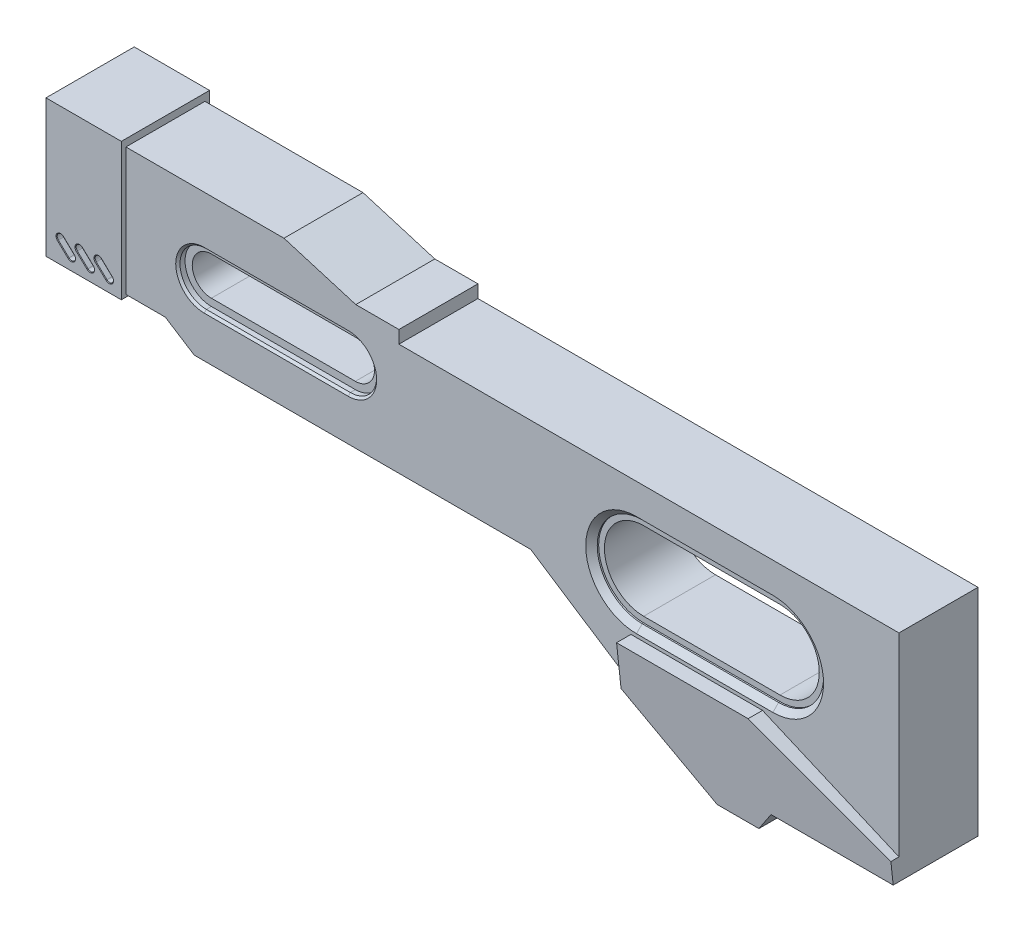
SolidWorks part; units mm, degrees
ref_plane "Front Plane" through (0, 0, 0) normal (0, 0, 1) x (1, 0, 0)
ref_plane "Top Plane" through (0, 0, 0) normal (0, 1, 0) x (1, 0, 0)
ref_plane "Right Plane" through (0, 0, 0) normal (1, 0, 0) x (0, 0, -1)
sketch "Sketch1" plane through (0, 0, 0) normal (0, 0, 1) x (1, 0, 0)
  line L0 (99.5486, 206.6349) -> (132.842, 206.6349)
  line L1 (132.842, 206.6349) -> (132.842, 207.688)
  line L2 (132.842, 207.688) -> (150.2564, 207.688)
  line L3 (150.2564, 207.688) -> (163.0366, 199.5431)
  line L4 (163.0366, 199.5431) -> (311.6766, 199.5431)
  line L5 (311.6766, 199.5431) -> (395.7493, 144.6965)
  line L6 (395.7493, 144.6965) -> (414.1914, 144.6965)
  line L7 (414.1914, 144.6965) -> (420.505, 153.713)
  line L8 (420.505, 153.713) -> (474.5094, 153.713)
  line L9 (474.5094, 153.713) -> (474.5094, 248.963)
  line L10 (474.5094, 248.963) -> (132.842, 248.963)
  line L11 (132.842, 248.963) -> (132.842, 251.0849)
  line L12 (132.842, 251.0849) -> (99.5486, 251.0849)
  line L13 (99.5486, 251.0849) -> (99.5486, 206.6349)
  dimension "D1" = 44.45
  dimension "D2" = 33.2933
  dimension "D3" = 33.2933
  dimension "D4" = 41.275
  dimension "D5" = 17.4144
  dimension "D6" = 15.155
  dimension "D7" = 49.4199
  dimension "D8" = 95.25
  dimension "D9" = 18.442
  dimension "D10" = 54.0045
  dimension "D11" = 100.3811
  dimension "D12" = 11.0073
  dimension "D13" = 148.64
  dimension "D14" = 1.0531
extrude "Boss-Extrude1" add sketch "Sketch1" along normal blind 17.4625 and the other way blind 17.4625 contours L10 L11 L12 L13 L0 L1 L2 L3 L4 L5 L6 L7 L8 L9
sketch "Sketch3" plane through (0, 0, 17.4625) normal (0, 0, 1) x (1, 0, 0)
  line L1 (99.5486, 251.0849) -> (132.842, 251.0849)
  line L2 (99.5486, 251.0849) -> (99.5486, 206.6349)
  line L3 (99.5486, 206.6349) -> (132.842, 206.6349)
  line L4 (132.842, 251.0849) -> (132.842, 206.6349)
extrude "Boss-Extrude2" add sketch "Sketch3" along normal blind 2.032
sketch "Sketch4" plane through (0, 0, -17.4625) normal (0, 0, -1) x (-1, 0, 0)
  line L1 (-99.5486, 251.0849) -> (-132.842, 251.0849)
  line L2 (-99.5486, 251.0849) -> (-99.5486, 206.6349)
  line L3 (-99.5486, 206.6349) -> (-132.842, 206.6349)
  line L4 (-132.842, 251.0849) -> (-132.842, 206.6349)
extrude "Boss-Extrude3" add sketch "Sketch4" along normal blind 2.032
sketch "Sketch8" plane through (0, 0, 17.4625) normal (0, 0, 1) x (1, 0, 0)
  line L0 (358.4861, 213.0728) -> (418.7637, 213.0728) construction
  line L1 (358.4861, 230.4099) -> (418.7637, 230.4099)
  line L2 (358.4861, 195.7357) -> (418.7637, 195.7357)
  line L3 (231.074, 230.4099) -> (167.4295, 230.4099) construction
  line L4 (231.074, 221.9555) -> (167.4295, 221.9555)
  line L5 (231.074, 238.8642) -> (167.4295, 238.8642)
  arc A0 (358.4861, 230.4099) -> (358.4861, 195.7357) centre (358.4861, 213.0728) ccw
  arc A1 (418.7637, 195.7357) -> (418.7637, 230.4099) centre (418.7637, 213.0728) ccw
  arc A2 (231.074, 221.9555) -> (231.074, 238.8642) centre (231.074, 230.4099) ccw
  arc A3 (167.4295, 238.8642) -> (167.4295, 221.9555) centre (167.4295, 230.4099) ccw
  point P2 (388.6249, 213.0728)
  point P9 (199.2518, 230.4099)
extrude "Cut-Extrude4" cut sketch "Sketch8" against normal through all
sketch "Sketch9" plane through (0, 0, 19.4945) normal (0, 0, 1) x (1, 0, 0)
  line L0 (105.9514, 216.6136) -> (110.6596, 212.1469) construction
  line L1 (107.1264, 217.8522) -> (111.8347, 213.3854)
  line L2 (104.7763, 215.3751) -> (109.4845, 210.9083)
  line L3 (114.3334, 216.6136) -> (119.0416, 212.1469) construction
  line L4 (115.5084, 217.8522) -> (120.2167, 213.3854)
  line L5 (113.1583, 215.3751) -> (117.8665, 210.9083)
  line L6 (122.7154, 216.6136) -> (127.4236, 212.1469) construction
  line L7 (123.8904, 217.8522) -> (128.5987, 213.3854)
  line L8 (121.5403, 215.3751) -> (126.2485, 210.9083)
  arc A0 (107.1264, 217.8522) -> (104.7763, 215.3751) centre (105.9514, 216.6136) ccw
  arc A1 (109.4845, 210.9083) -> (111.8347, 213.3854) centre (110.6596, 212.1469) ccw
  arc A2 (115.5084, 217.8522) -> (113.1583, 215.3751) centre (114.3334, 216.6136) ccw
  arc A3 (117.8665, 210.9083) -> (120.2167, 213.3854) centre (119.0416, 212.1469) ccw
  arc A4 (123.8904, 217.8522) -> (121.5403, 215.3751) centre (122.7154, 216.6136) ccw
  arc A5 (126.2485, 210.9083) -> (128.5987, 213.3854) centre (127.4236, 212.1469) ccw
  point P2 (108.3055, 214.3802)
  point P10 (116.6875, 214.3802)
  point P17 (125.0695, 214.3802)
  dimension "D1" = 3
extrude "Cut-Extrude5" cut sketch "Sketch9" against normal blind 2.54
sketch "Sketch10" plane through (0, 0, 17.4625) normal (0, 0, 1) x (1, 0, 0)
  line L8 (167.4295, 218.7805) -> (231.074, 218.7805)
  line L9 (231.074, 242.0392) -> (167.4295, 242.0392)
  line L10 (167.4295, 218.7805) -> (231.074, 218.7805)
  line L11 (231.074, 242.0392) -> (167.4295, 242.0392)
  arc A6 (231.074, 218.7805) -> (231.074, 242.0392) centre (231.074, 230.4099) ccw
  arc A7 (167.4295, 242.0392) -> (167.4295, 218.7805) centre (167.4295, 230.4099) ccw
  arc A8 (231.074, 218.7805) -> (231.074, 242.0392) centre (231.074, 230.4099) ccw
  arc A9 (167.4295, 242.0392) -> (167.4295, 218.7805) centre (167.4295, 230.4099) ccw
  dimension "D1" = 3.175
extrude "Cut-Extrude6" cut sketch "Sketch10" against normal blind 3.175
chamfer "Chamfer1" distance 0.9525 angle 45 4 edges at (242.7033, 230.4099, 17.4625) (199.2518, 242.0392, 17.4625) (199.2518, 218.7805, 17.4625) (155.8002, 230.4099, 17.4625)
chamfer "Chamfer2" distance 0.254 angle 45 12 edges at (123.8944, 213.1417, 19.4945) (128.6622, 210.9718, 19.4945) (121.4768, 217.7887, 19.4945) (126.2445, 215.6188, 19.4945) (115.5124, 213.1417, 19.4945) (120.2802, 210.9718, 19.4945) (113.0948, 217.7887, 19.4945) (117.8625, 215.6188, 19.4945) (107.1304, 213.1417, 19.4945) (111.8982, 210.9718, 19.4945) (104.7128, 217.7887, 19.4945) (109.4805, 215.6188, 19.4945)
sketch "Sketch12" plane through (0, 0, 17.4625) normal (0, 0, 1) x (1, 0, 0)
  line L6 (358.4861, 193.1957) -> (418.7637, 193.1957)
  line L7 (418.7637, 232.9499) -> (358.4861, 232.9499)
  line L8 (358.4861, 193.1957) -> (418.7637, 193.1957)
  line L9 (418.7637, 232.9499) -> (358.4861, 232.9499)
  arc A8 (418.7637, 193.1957) -> (418.7637, 232.9499) centre (418.7637, 213.0728) ccw
  arc A9 (358.4861, 232.9499) -> (358.4861, 193.1957) centre (358.4861, 213.0728) ccw
  arc A10 (418.7637, 193.1957) -> (418.7637, 232.9499) centre (418.7637, 213.0728) ccw
  arc A11 (358.4861, 232.9499) -> (358.4861, 193.1957) centre (358.4861, 213.0728) ccw
  dimension "D1" = 2.54
extrude "Cut-Extrude7" cut sketch "Sketch12" against normal blind 3.175
chamfer "Chamfer3" distance 2.54 angle 45 4 edges at (438.6408, 213.0728, 17.4625) (388.6249, 232.9499, 17.4625) (388.6249, 193.1957, 17.4625) (338.6091, 213.0728, 17.4625)
sketch "Sketch14" plane through (0, 0, 17.4625) normal (0, 0, 1) x (1, 0, 0)
  line L0 (356.0379, 170.603) -> (356.0379, 189.1535)
  line L1 (311.6766, 199.5431) -> (395.7493, 144.6965) construction
  line L2 (356.0379, 189.1535) -> (414.1914, 189.1535)
  line L3 (414.1914, 189.1535) -> (474.5094, 163.2394)
  line L4 (474.5094, 153.713) -> (474.5094, 248.963) construction
  line L5 (474.5094, 163.2394) -> (474.5094, 153.713)
  line L6 (474.5094, 153.713) -> (420.505, 153.713)
  line L7 (420.505, 153.713) -> (414.1914, 144.6965)
  line L8 (414.1914, 144.6965) -> (395.7493, 144.6965)
  line L9 (395.7493, 144.6965) -> (356.0379, 170.603)
extrude "Boss-Extrude4" add sketch "Sketch14" along normal blind 6.35
sketch "Sketch15" plane through (209.9379, -147.0027, 0) normal (0.8191, -0.5736, 0) x (0, 0, -1)
  line L0 (17.4625, 356.1009) -> (-23.8125, 356.1009) construction
  point P0 (-19.05, 356.1009)
  dimension "D1" = 4.7625
ref_plane "Plane1" through (0, -0.3759, 3.509) normal (0, -0.1065, 0.9943) x (1, 0, 0)
sketch "Sketch16" plane through (0, -0.3759, 3.509) normal (0, -0.1065, 0.9943) x (1, 0, 0)
  line L1 (334.5194, 202.4407) -> (488.3818, 202.4407)
  line L2 (334.5194, 202.4407) -> (334.5194, 128.8391)
  line L3 (334.5194, 128.8391) -> (488.3818, 128.8391)
  line L4 (488.3818, 202.4407) -> (488.3818, 128.8391)
extrude "Cut-Extrude8" cut sketch "Sketch16" along normal through all
sketch "Sketch17" plane through (0, 0, 19.4945) normal (0, 0, 1) x (1, 0, 0)
  line L0 (132.842, 206.6349) -> (132.842, 251.0849) construction
  line L1 (99.5486, 251.0849) -> (132.842, 251.0849)
  line L2 (99.5486, 251.0849) -> (99.5486, 267.3015)
  line L3 (99.5486, 267.3015) -> (132.842, 267.3015)
  line L4 (132.842, 251.0849) -> (132.842, 267.3015)
  line L5 (213.6718, 257.7765) -> (194.6218, 257.7765) construction
  dimension "D1" = 9.525
extrude "Boss-Extrude5" add sketch "Sketch17" against normal up to surface (38.989 mm away) up to face at (116.1953, 228.8599, -19.4945)
sketch "Sketch18" plane through (0, 0, 17.4625) normal (0, 0, 1) x (1, 0, 0)
  line L0 (132.842, 248.963) -> (132.842, 264.1265)
  line L1 (132.842, 206.6349) -> (132.842, 267.3015) construction
  line L2 (132.842, 264.1265) -> (202.692, 264.1265)
  line L3 (202.692, 264.1265) -> (234.442, 254.6015)
  line L4 (321.6218, 254.6015) -> (218.4343, 254.6015) construction
  line L5 (234.442, 254.6015) -> (253.492, 254.6015)
  line L6 (253.492, 254.6015) -> (253.492, 248.963)
  line L7 (474.5094, 248.963) -> (132.842, 248.963) construction
  line L8 (253.492, 248.963) -> (132.842, 248.963)
  line L9 (132.842, 267.3015) -> (99.5486, 267.3015) construction
  dimension "D1" = 3.175
  dimension "D2" = 69.85
  dimension "D3" = 19.05
  dimension "D4" = 120.65
extrude "Boss-Extrude6" add sketch "Sketch18" against normal up to surface (34.925 mm away) up to face at (199.2518, 230.4099, -17.4625)
